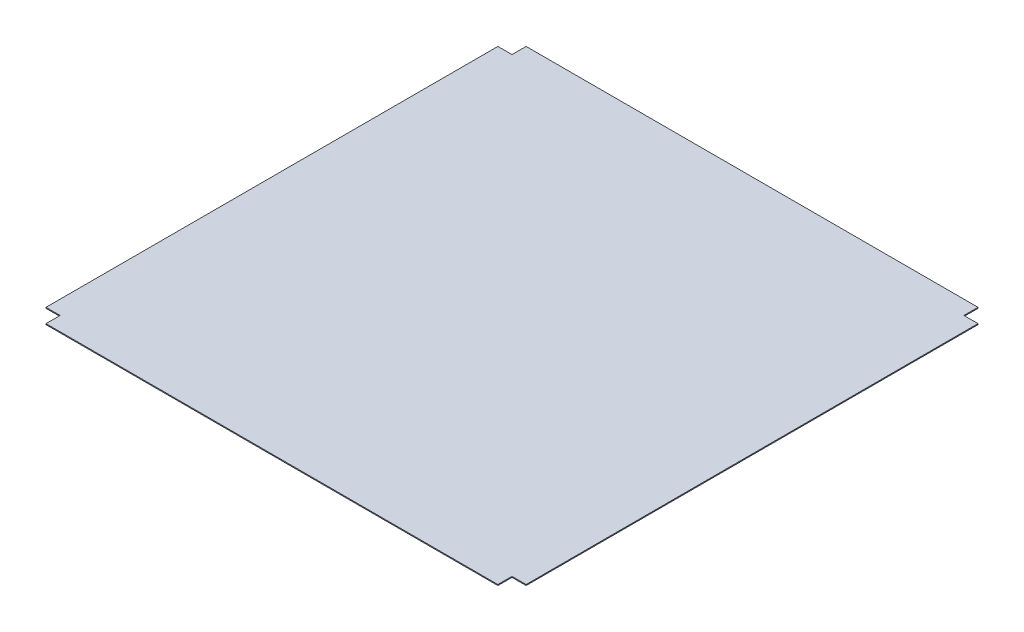
SolidWorks part; units mm, degrees
material "1060 Alloy"
ref_plane "Front" through (0, 0, 0) normal (0, 0, 1) x (1, 0, 0)
ref_plane "Top" through (0, 0, 0) normal (0, 1, 0) x (1, 0, 0)
ref_plane "Right" through (0, 0, 0) normal (1, 0, 0) x (0, 0, -1)
ref_axis "Axis1" through (0, 62.7688, 0) along (0, -1, 0)
sketch "Sketch1" plane through (0, 0, 0) normal (0, 1, 0) x (1, 0, 0)
  line L0 (0, 0) -> (0, 297.7889) construction
  line L1 (0, 0) -> (271.176, 0) construction
  line L3 (-255, 255) -> (255, 255)
  line L4 (-255, 255) -> (-255, -255)
  line L5 (-255, -255) -> (255, -255)
  line L6 (255, 255) -> (255, -255)
  point P8 (0, 255)
  point P9 (255, 0)
  dimension "D1" = 510
  dimension "D2" = 510
extrude "Extrude1" add sketch "Sketch1" along normal blind 1
sketch "Sketch3" plane through (0, 1, 0) normal (0, 1, 0) x (-1, 0, 0)
  line L0 (-255, 0) -> (0, 0) construction
  line L1 (-255, 255) -> (-255, -255) construction
  line L2 (0, 0) -> (0, 226.4769) construction
  line L4 (-255, -255) -> (-240, -255)
  line L5 (-255, -255) -> (-255, -240)
  line L6 (-255, -240) -> (-240, -240)
  line L7 (-240, -255) -> (-240, -240)
  line L8 (-255, 255) -> (-240, 255)
  line L9 (-255, 255) -> (-255, 240)
  line L10 (-255, 240) -> (-240, 240)
  line L11 (-240, 255) -> (-240, 240)
  line L12 (255, 255) -> (240, 255)
  line L13 (255, 255) -> (255, 240)
  line L14 (255, 240) -> (240, 240)
  line L15 (240, 255) -> (240, 240)
  line L16 (255, -255) -> (240, -255)
  line L17 (255, -255) -> (255, -240)
  line L18 (255, -240) -> (240, -240)
  line L19 (240, -255) -> (240, -240)
  dimension "D1" = 15
extrude "Cut-Extrude1" cut sketch "Sketch3" against normal through all
